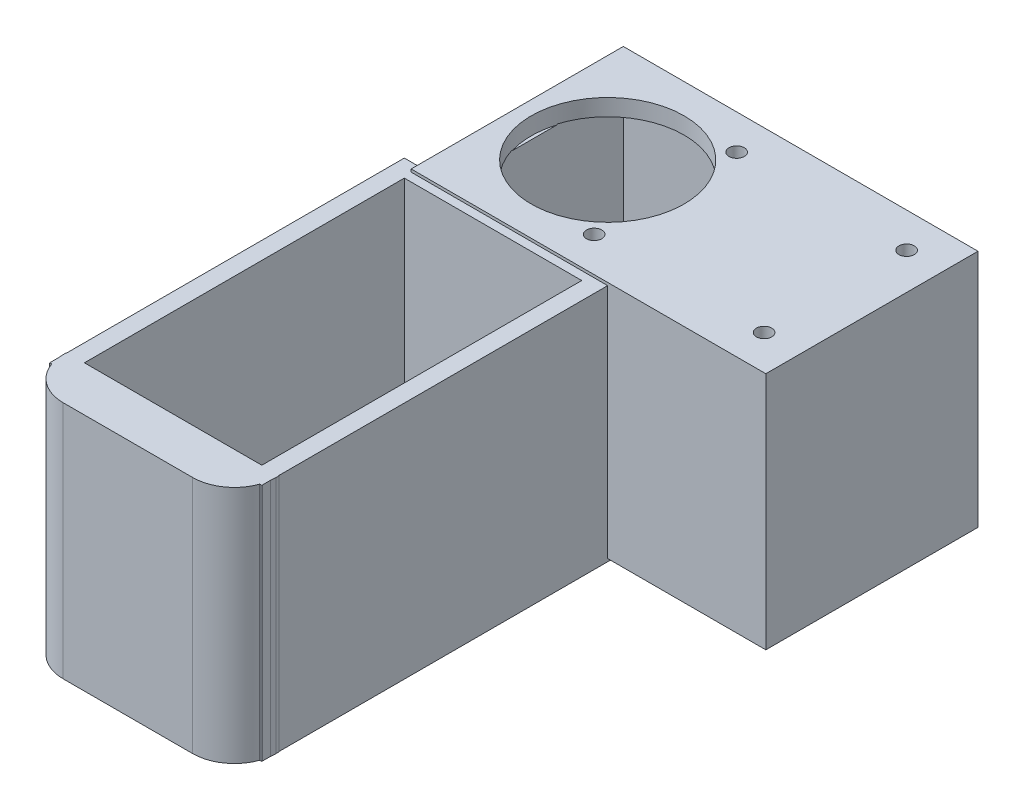
SolidWorks part; units mm, degrees
ref_plane "Front Plane" through (0, 0, 0) normal (0, 0, 1) x (1, 0, 0)
ref_plane "Top Plane" through (0, 0, 0) normal (0, 1, 0) x (1, 0, 0)
ref_plane "Right Plane" through (0, 0, 0) normal (1, 0, 0) x (0, 0, -1)
ref_plane "PZ_m38_010" through (0, 0, -38.01) normal (0, 0, 1) x (1, 0, 0)
sketch "S_box1" plane through (0, 0, -38.01) normal (0, 0, 1) x (1, 0, 0)
  line L0 (-15.26, -37.025) -> (15.26, -37.025)
  line L1 (15.26, -37.025) -> (15.26, -2.625)
  line L2 (15.26, -2.625) -> (-15.26, -2.625)
  line L3 (-15.26, -2.625) -> (-15.26, -37.025)
  dimension "P1" = 15.26
  dimension "P2" = 37.025
  dimension "P3" = 15.26
  dimension "P4" = 37.025
  dimension "P5" = 15.26
  dimension "P6" = 2.625
  dimension "P7" = 15.26
  dimension "P8" = 2.625
extrude "Boss_1" add sketch "S_box1" along normal blind 2.5
ref_plane "PZ_p10_510" through (0, 0, 10.51) normal (0, 0, 1) x (1, 0, 0)
sketch "S_box2" plane through (0, 0, 10.51) normal (0, 0, 1) x (1, 0, 0)
  line L0 (-15.26, -37.025) -> (15.26, -37.025)
  line L1 (15.26, -37.025) -> (15.26, -2.625)
  line L2 (15.26, -2.625) -> (-15.26, -2.625)
  line L3 (-15.26, -2.625) -> (-15.26, -37.025)
  dimension "P1" = 15.26
  dimension "P2" = 37.025
  dimension "P3" = 15.26
  dimension "P4" = 37.025
  dimension "P5" = 15.26
  dimension "P6" = 2.625
  dimension "P7" = 15.26
  dimension "P8" = 2.625
extrude "Boss_2" add sketch "S_box2" along normal blind 2.5
sketch "S_box3" plane through (0, 0, -38.01) normal (0, 0, 1) x (1, 0, 0)
  line L0 (-15.26, -37.025) -> (-12.76, -37.025)
  line L1 (-12.76, -37.025) -> (-12.76, -2.625)
  line L2 (-12.76, -2.625) -> (-15.26, -2.625)
  line L3 (-15.26, -2.625) -> (-15.26, -37.025)
  dimension "P1" = 15.26
  dimension "P2" = 37.025
  dimension "P3" = 12.76
  dimension "P4" = 37.025
  dimension "P5" = 12.76
  dimension "P6" = 2.625
  dimension "P7" = 15.26
  dimension "P8" = 2.625
extrude "Boss_3" add sketch "S_box3" along normal blind 51.02
sketch "S_box4" plane through (0, 0, -38.01) normal (0, 0, 1) x (1, 0, 0)
  line L0 (12.76, -37.025) -> (15.26, -37.025)
  line L1 (15.26, -37.025) -> (15.26, -2.625)
  line L2 (15.26, -2.625) -> (12.76, -2.625)
  line L3 (12.76, -2.625) -> (12.76, -37.025)
  dimension "P1" = 12.76
  dimension "P2" = 37.025
  dimension "P3" = 15.26
  dimension "P4" = 37.025
  dimension "P5" = 15.26
  dimension "P6" = 2.625
  dimension "P7" = 12.76
  dimension "P8" = 2.625
extrude "Boss_4" add sketch "S_box4" along normal blind 51.02
sketch "S_box5" plane through (0, 0, -38.01) normal (0, 0, 1) x (1, 0, 0)
  line L0 (-15.26, -37.025) -> (15.26, -37.025)
  line L1 (15.26, -37.025) -> (15.26, -34.625)
  line L2 (15.26, -34.625) -> (-15.26, -34.625)
  line L3 (-15.26, -34.625) -> (-15.26, -37.025)
  dimension "P1" = 15.26
  dimension "P2" = 37.025
  dimension "P3" = 15.26
  dimension "P4" = 37.025
  dimension "P5" = 15.26
  dimension "P6" = 34.625
  dimension "P7" = 15.26
  dimension "P8" = 34.625
extrude "Boss_5" add sketch "S_box5" along normal blind 51.02
ref_plane "PZ_m67_260" through (0, 0, -67.26) normal (0, 0, 1) x (1, 0, 0)
sketch "S_box6" plane through (0, 0, -67.26) normal (0, 0, 1) x (1, 0, 0)
  line L0 (-13.01, -36.625) -> (-10.51, -36.625)
  line L1 (-10.51, -36.625) -> (-10.51, -2.225)
  line L2 (-10.51, -2.225) -> (-13.01, -2.225)
  line L3 (-13.01, -2.225) -> (-13.01, -36.625)
  dimension "P1" = 13.01
  dimension "P2" = 36.625
  dimension "P3" = 10.51
  dimension "P4" = 36.625
  dimension "P5" = 10.51
  dimension "P6" = 2.225
  dimension "P7" = 13.01
  dimension "P8" = 2.225
extrude "Boss_6" add sketch "S_box6" along normal blind 30.52
sketch "S_box7" plane through (0, 0, -67.26) normal (0, 0, 1) x (1, 0, 0)
  line L0 (35.51, -36.625) -> (38.01, -36.625)
  line L1 (38.01, -36.625) -> (38.01, -2.225)
  line L2 (38.01, -2.225) -> (35.51, -2.225)
  line L3 (35.51, -2.225) -> (35.51, -36.625)
  dimension "P1" = 35.51
  dimension "P2" = 36.625
  dimension "P3" = 38.01
  dimension "P4" = 36.625
  dimension "P5" = 38.01
  dimension "P6" = 2.225
  dimension "P7" = 35.51
  dimension "P8" = 2.225
extrude "Boss_7" add sketch "S_box7" along normal blind 30.52
sketch "S_box8" plane through (0, 0, -67.26) normal (0, 0, 1) x (1, 0, 0)
  line L0 (-13.01, -36.625) -> (38.01, -36.625)
  line L1 (38.01, -36.625) -> (38.01, -2.225)
  line L2 (38.01, -2.225) -> (-13.01, -2.225)
  line L3 (-13.01, -2.225) -> (-13.01, -36.625)
  dimension "P1" = 13.01
  dimension "P2" = 36.625
  dimension "P3" = 38.01
  dimension "P4" = 36.625
  dimension "P5" = 38.01
  dimension "P6" = 2.225
  dimension "P7" = 13.01
  dimension "P8" = 2.225
extrude "Boss_8" add sketch "S_box8" along normal blind 2.5
ref_plane "PZ_m39_240" through (0, 0, -39.24) normal (0, 0, 1) x (1, 0, 0)
sketch "S_box9" plane through (0, 0, -39.24) normal (0, 0, 1) x (1, 0, 0)
  line L0 (-13.01, -36.625) -> (38.01, -36.625)
  line L1 (38.01, -36.625) -> (38.01, -2.225)
  line L2 (38.01, -2.225) -> (-13.01, -2.225)
  line L3 (-13.01, -2.225) -> (-13.01, -36.625)
  dimension "P1" = 13.01
  dimension "P2" = 36.625
  dimension "P3" = 38.01
  dimension "P4" = 36.625
  dimension "P5" = 38.01
  dimension "P6" = 2.225
  dimension "P7" = 13.01
  dimension "P8" = 2.225
extrude "Boss_9" add sketch "S_box9" along normal blind 2.5
sketch "S_box10" plane through (0, 0, -67.26) normal (0, 0, 1) x (1, 0, 0)
  line L0 (-13.01, -4.625) -> (38.01, -4.625)
  line L1 (38.01, -4.625) -> (38.01, -2.225)
  line L2 (38.01, -2.225) -> (-13.01, -2.225)
  line L3 (-13.01, -2.225) -> (-13.01, -4.625)
  dimension "P1" = 13.01
  dimension "P2" = 4.625
  dimension "P3" = 38.01
  dimension "P4" = 4.625
  dimension "P5" = 38.01
  dimension "P6" = 2.225
  dimension "P7" = 13.01
  dimension "P8" = 2.225
extrude "Boss_10" add sketch "S_box10" along normal blind 30.52
ref_plane "PY_m37_025" through (0, -37.025, 0) normal (0, 1, 0) x (1, 0, 0)
sketch "S_prism11" plane through (0, -37.025, 0) normal (0, 1, 0) x (1, 0, 0)
  line L0 (-15.31, -10.56) -> (15.31, -10.56)
  line L1 (15.31, -10.56) -> (15.31, -11.01)
  line L2 (9.31, -17.01) -> (-9.31, -17.01)
  line L3 (-15.31, -11.01) -> (-15.31, -10.56)
  arc A0 (15.31, -11.01) -> (9.31, -17.01) centre (9.3099, -11.0099) cw
  arc A1 (-9.31, -17.01) -> (-15.31, -11.01) centre (-9.3099, -11.0099) cw
extrude "Boss_11" add sketch "S_prism11" along normal blind 34.4
ref_plane "PY_m37_125" through (0, -37.125, 0) normal (0, 1, 0) x (1, 0, 0)
sketch "S_hole12" plane through (0, -37.125, 0) normal (0, 1, 0) x (1, 0, 0)
  circle A0 centre (0, 0) radius 11
  dimension "D1_S_hole12" = 22
extrude "Hole_12" cut sketch "S_hole12" along normal blind 2.6
sketch "S_hole13" plane through (0, -37.125, 0) normal (0, 1, 0) x (1, 0, 0)
  circle A0 centre (-10.25, 8.3) radius 1.1
  dimension "D1_S_hole13" = 2.2
  dimension "P2" = 10.25
  dimension "P3" = 8.3
extrude "Hole_13" cut sketch "S_hole13" along normal blind 2.6
sketch "S_hole14" plane through (0, -37.125, 0) normal (0, 1, 0) x (1, 0, 0)
  circle A0 centre (10.25, 8.3) radius 1.1
  dimension "D1_S_hole14" = 2.2
  dimension "P2" = 10.25
  dimension "P3" = 8.3
extrude "Hole_14" cut sketch "S_hole14" along normal blind 2.6
sketch "S_hole15" plane through (0, -37.125, 0) normal (0, 1, 0) x (1, 0, 0)
  circle A0 centre (-10.25, 32.75) radius 1.1
  dimension "D1_S_hole15" = 2.2
  dimension "P2" = 10.25
  dimension "P3" = 32.75
extrude "Hole_15" cut sketch "S_hole15" along normal blind 2.6
sketch "S_hole16" plane through (0, -37.125, 0) normal (0, 1, 0) x (1, 0, 0)
  circle A0 centre (10.25, 32.75) radius 1.1
  dimension "D1_S_hole16" = 2.2
  dimension "P2" = 10.25
  dimension "P3" = 32.75
extrude "Hole_16" cut sketch "S_hole16" along normal blind 2.6
ref_plane "PY_m4_725" through (0, -4.725, 0) normal (0, 1, 0) x (1, 0, 0)
sketch "S_hole17" plane through (0, -4.725, 0) normal (0, 1, 0) x (1, 0, 0)
  circle A0 centre (0, 52) radius 11
  dimension "D1_S_hole17" = 22
  dimension "P2" = 52
extrude "Hole_17" cut sketch "S_hole17" along normal blind 2.6
sketch "S_hole18" plane through (0, -4.725, 0) normal (0, 1, 0) x (1, 0, 0)
  circle A0 centre (8.3, 62.25) radius 1.1
  dimension "D1_S_hole18" = 2.2
  dimension "P2" = 8.3
  dimension "P3" = 62.25
extrude "Hole_18" cut sketch "S_hole18" along normal blind 2.6
sketch "S_hole19" plane through (0, -4.725, 0) normal (0, 1, 0) x (1, 0, 0)
  circle A0 centre (8.3, 41.75) radius 1.1
  dimension "D1_S_hole19" = 2.2
  dimension "P2" = 8.3
  dimension "P3" = 41.75
extrude "Hole_19" cut sketch "S_hole19" along normal blind 2.6
sketch "S_hole20" plane through (0, -4.725, 0) normal (0, 1, 0) x (1, 0, 0)
  circle A0 centre (32.75, 62.25) radius 1.1
  dimension "D1_S_hole20" = 2.2
  dimension "P2" = 32.75
  dimension "P3" = 62.25
extrude "Hole_20" cut sketch "S_hole20" along normal blind 2.6
sketch "S_hole21" plane through (0, -4.725, 0) normal (0, 1, 0) x (1, 0, 0)
  circle A0 centre (32.75, 41.75) radius 1.1
  dimension "D1_S_hole21" = 2.2
  dimension "P2" = 32.75
  dimension "P3" = 41.75
extrude "Hole_21" cut sketch "S_hole21" along normal blind 2.6
equation "\"plate_t\" = 3"
equation "\"clearance\" = 0.4"
